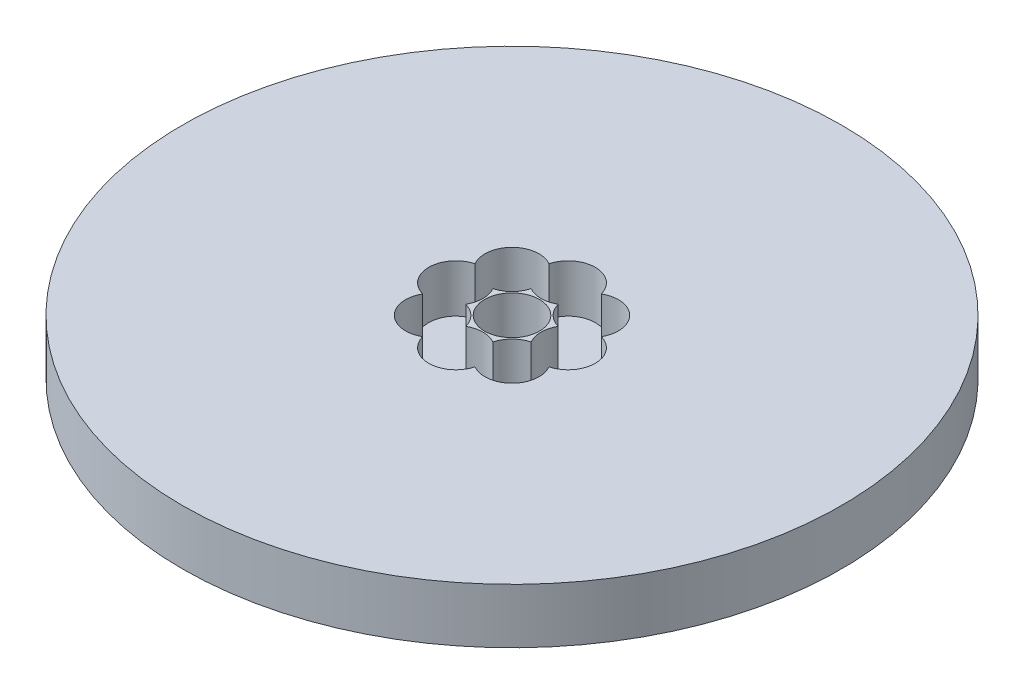
SolidWorks part; units mm, degrees
ref_plane "Front Plane" through (0, 0, 0) normal (0, 0, 1) x (1, 0, 0)
ref_plane "Top Plane" through (0, 0, 0) normal (0, 1, 0) x (1, 0, 0)
ref_plane "Right Plane" through (0, 0, 0) normal (1, 0, 0) x (0, 0, -1)
sketch "Sketch1" plane through (0, 0, 0) normal (0, 1, 0) x (1, 0, 0)
  circle A0 centre (0, 0) radius 60
  dimension "FLANGE_OD" = 120
extrude "Boss-Extrude1" add sketch "Sketch1" along normal blind 10
sketch "Sketch2" plane through (0, 0, 0) normal (0, 1, 0) x (1, 0, 0)
  circle A0 centre (0, 0) radius 5
  dimension "BORE_D" = 10
extrude "Cut-Extrude1" cut sketch "Sketch2" along normal through all
sketch "Sketch3" plane through (0, 10, 0) normal (0, 1, 0) x (1, 0, 0)
  circle A0 centre (0, 0) radius 10.2221 construction
  circle A1 centre (-10.2221, 0) radius 4.9312
  dimension "BOLT_D" = 9.8624
  dimension "BOLT_PCD" = 20.4441
extrude "Cut-Extrude2" cut sketch "Sketch3" against normal blind 8.7291
pattern_circular "CirPattern1" count 8 over 360 about axis through (0, 0, 0) along (0, 1, 0) of "Cut-Extrude2"
